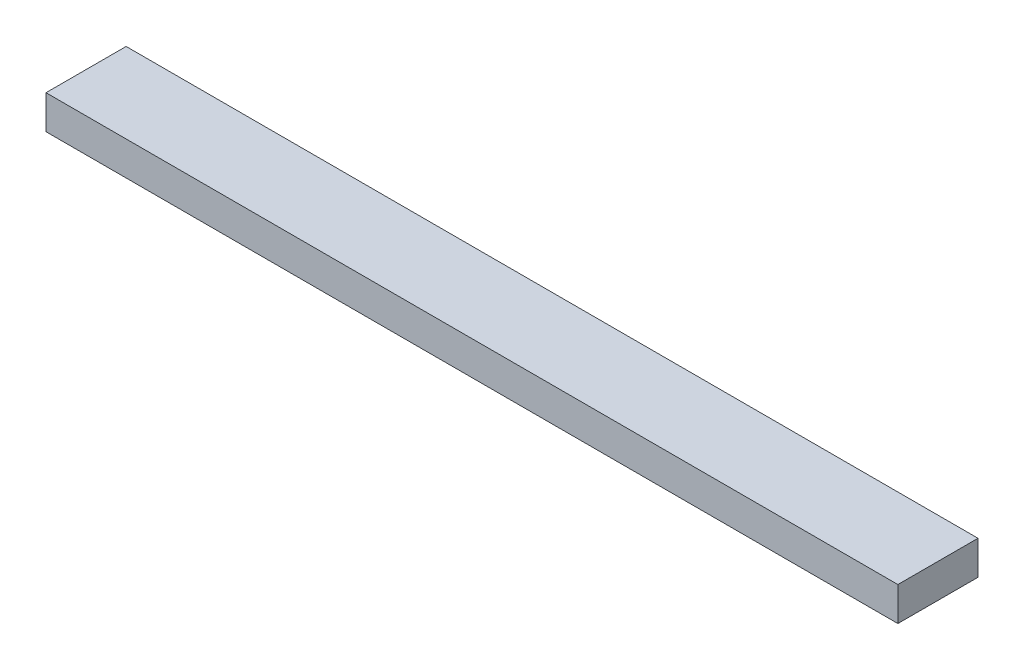
SolidWorks part; units mm, degrees
ref_plane "Front Plane" through (0, 0, 0) normal (0, 0, 1) x (1, 0, 0)
ref_plane "Top Plane" through (0, 0, 0) normal (0, 1, 0) x (1, 0, 0)
ref_plane "Right Plane" through (0, 0, 0) normal (1, 0, 0) x (0, 0, -1)
sketch "Sketch1" plane through (0, 0, 0) normal (1, 0, 0) x (0, 0, -1)
  line L1 (0, 0) -> (30.1, 0)
  line L2 (0, 0) -> (0, 12.7)
  line L3 (0, 12.7) -> (30.1, 12.7)
  line L4 (30.1, 0) -> (30.1, 12.7)
  dimension "D1" = 30.1
  dimension "D2" = 12.7
extrude "Boss-Extrude1" add sketch "Sketch1" along normal blind 320
sketch "Sketch2" plane through (0, 0, 0) normal (0, 0, 1) x (1, 0, 0)
  line L0 (0, 0) -> (320, 0) construction
  point P4 (160, 0)
